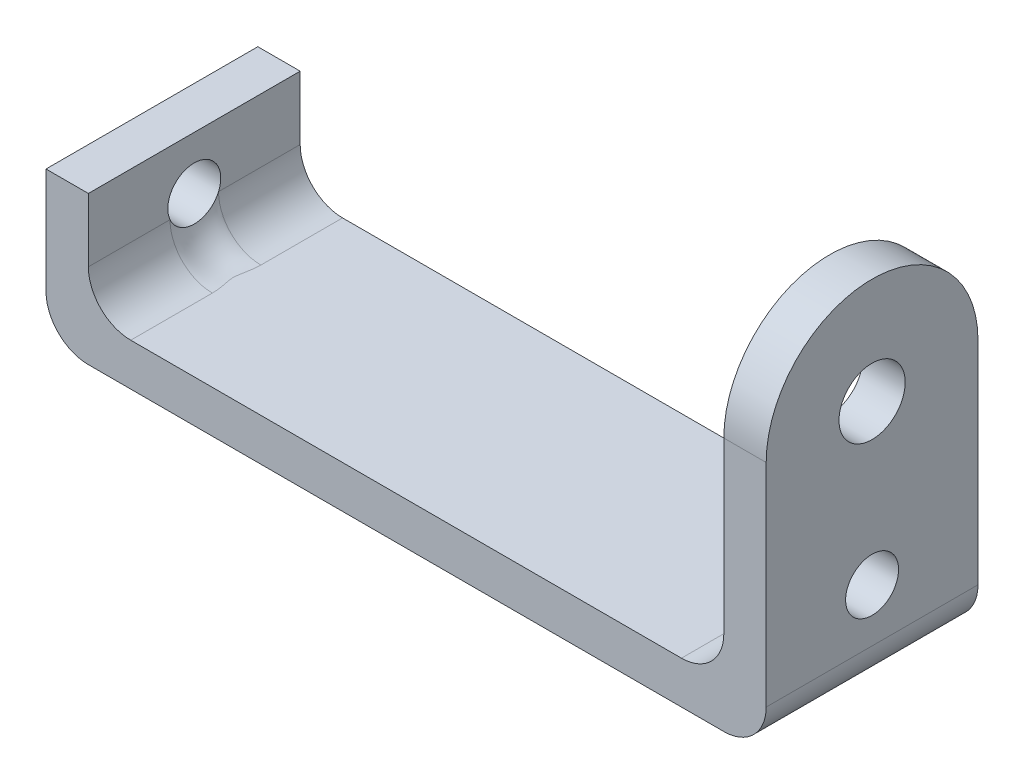
SolidWorks part; units mm, degrees
ref_plane "Front Plane" through (0, 0, 0) normal (0, 0, 1) x (1, 0, 0)
ref_plane "Top Plane" through (0, 0, 0) normal (0, 1, 0) x (1, 0, 0)
ref_plane "Right Plane" through (0, 0, 0) normal (1, 0, 0) x (0, 0, -1)
sketch "Sketch1" plane through (0, 0, 0) normal (0, 1, 0) x (1, 0, 0)
  line L1 (-38.1, -12.7) -> (38.1, -12.7)
  line L2 (-38.1, -12.7) -> (-38.1, 12.7)
  line L3 (-38.1, 12.7) -> (38.1, 12.7)
  line L4 (38.1, -12.7) -> (38.1, 12.7)
  line L5 (-38.1, -12.7) -> (38.1, 12.7) construction
  line L6 (-38.1, 12.7) -> (38.1, -12.7) construction
  point P0 (0, 0)
  dimension "D1" = 25.4
  dimension "D2" = 76.2
extrude "Boss-Extrude1" add sketch "Sketch1" along normal blind 5.08 contours L2 L1 L4 L3
sketch "Sketch3" plane through (38.1, 0, 0) normal (1, 0, 0) x (0, 0, -1)
  line L0 (12.7, 5.08) -> (12.7, 0) construction
  line L1 (-12.7, 5.08) -> (12.7, 5.08)
  line L2 (-12.7, 5.08) -> (-12.7, 43.18)
  line L3 (-12.7, 43.18) -> (12.7, 43.18)
  line L4 (12.7, 5.08) -> (12.7, 43.18)
  line L5 (0, 43.18) -> (0, 0) construction
  line L6 (-12.7, 0) -> (12.7, 0) construction
  circle A0 centre (0, 30.48) radius 12.7
  circle A1 centre (0, 11.43) radius 3.175
  circle A2 centre (0, 30.48) radius 3.9688
  line M10 (12.7, 5.08) -> (-12.7, 5.08)
  dimension "D3" = 6.35
  dimension "D4" = 7.9375
  dimension "D1" = 38.1
  dimension "D2" = 19.05
extrude "Boss-Extrude2" add sketch "Sketch3" along normal blind 5.08 separate body contours L5 A0 L2 L1 A1 | A0 L5 A1 L4 M10 | L5 A0 A2 | A0 L5 A2
sketch "Sketch4" plane through (-38.1, 0, 0) normal (-1, 0, 0) x (0, 0, 1)
  line L0 (-12.7, 11.43) -> (12.7, 11.43) construction
  line L1 (-12.7, 5.08) -> (12.7, 5.08)
  line L2 (-12.7, 5.08) -> (-12.7, 17.78)
  line L3 (-12.7, 17.78) -> (12.7, 17.78)
  line L4 (12.7, 5.08) -> (12.7, 17.78)
  circle A0 centre (0, 11.43) radius 3.175
  circle A1 centre (0, 11.43) radius 3.175 construction
  point P11 (0, 11.43)
extrude "Boss-Extrude3" add sketch "Sketch4" along normal blind 5.08 separate body
sketch "Sketch5" plane through (38.1, 0, 0) normal (1, 0, 0) x (0, 0, -1)
  line L4 (-12.7, 0) -> (12.7, 0)
  line L5 (12.7, 0) -> (12.7, 5.08)
  line L6 (12.7, 5.08) -> (-12.7, 5.08)
  line L7 (-12.7, 5.08) -> (-12.7, 0)
  line L8 (-12.7, 0) -> (12.7, 0)
  line L9 (12.7, 0) -> (12.7, 5.08)
  line L10 (12.7, 5.08) -> (-12.7, 5.08)
  line L11 (-12.7, 5.08) -> (-12.7, 0)
  dimension "D1" = 0
revolve "Revolve2" add sketch "Sketch5" angle 90 about L10
fillet "Fillet1" radius 5.08 1 edges at (38.1, 5.08, 0)
sketch "Sketch7" plane through (-38.1, 0, 0) normal (-1, 0, 0) x (0, 0, 1)
  line L4 (-12.7, 0) -> (12.7, 0)
  line L5 (12.7, 0) -> (12.7, 5.08)
  line L6 (12.7, 5.08) -> (-12.7, 5.08)
  line L7 (-12.7, 5.08) -> (-12.7, 0)
  line L8 (-12.7, 0) -> (12.7, 0)
  line L9 (12.7, 0) -> (12.7, 5.08)
  line L10 (12.7, 5.08) -> (-12.7, 5.08)
  line L11 (-12.7, 5.08) -> (-12.7, 0)
  dimension "D1" = 0
revolve "Revolve3" add sketch "Sketch7" angle 90 about L10
fillet "Fillet3" radius 5.08 1 edges at (-38.1, 5.08, 0)
